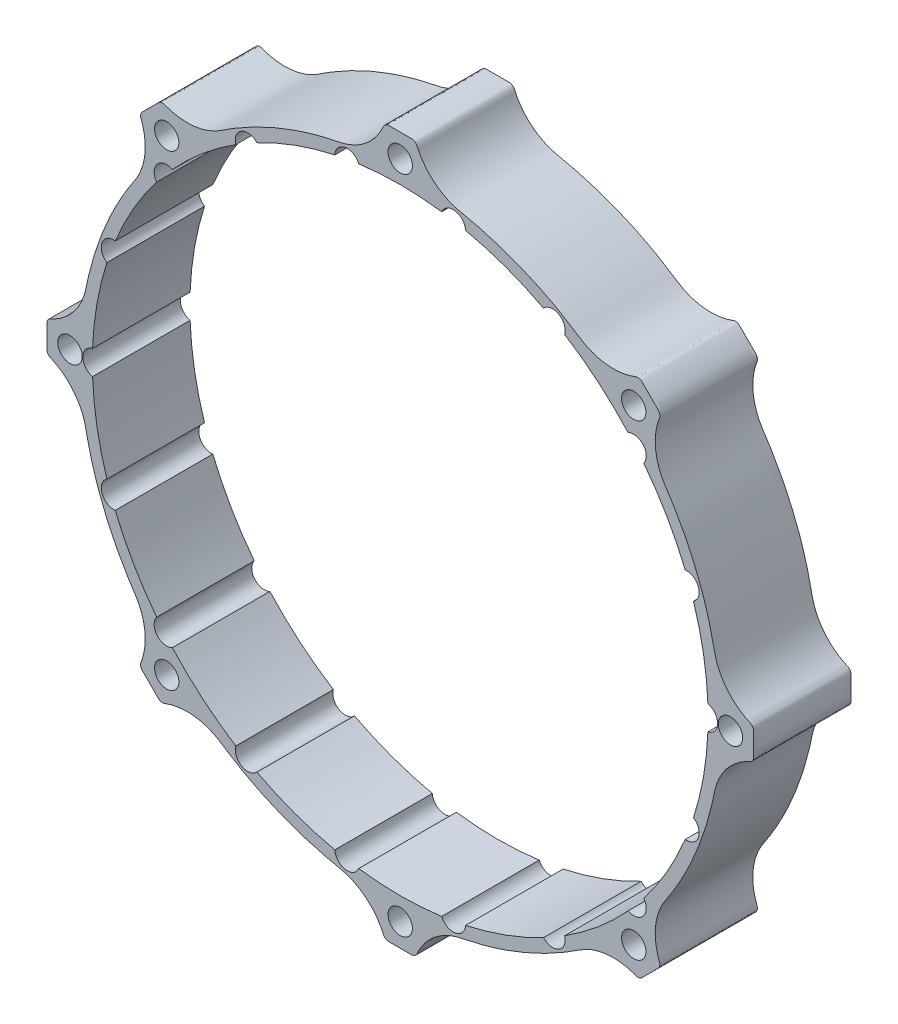
SolidWorks part; units mm, degrees
material "7075-T6, Plate (SS)"
ref_plane "Front Plane" through (0, 0, 0) normal (0, 0, 1) x (1, 0, 0)
ref_plane "Top Plane" through (0, 0, 0) normal (0, 1, 0) x (1, 0, 0)
ref_plane "Right Plane" through (0, 0, 0) normal (1, 0, 0) x (0, 0, -1)
sketch "Sketch1" plane through (0, 0, 0) normal (0, 0, 1) x (1, 0, 0)
  line L0 (0, 0) -> (0, 54.1614) construction
  line L1 (0, 0) -> (-8.6824, 49.2404) construction
  arc A0 (-6.7951, 50.0407) -> (-10.7296, 49.347) centre (-8.6824, 49.2404) ccw
  arc A36 (-10.7296, 49.347) -> (-23.5003, 44.6989) centre (0, 0) ccw
  circle A53 centre (0, 0) radius 50 construction
  arc A54 (10.7296, 49.347) -> (6.7951, 50.0407) centre (8.6824, 49.2404) ccw
  arc A55 (26.9602, 42.7012) -> (23.5003, 44.6989) centre (25, 43.3013) ccw
  arc A56 (39.939, 30.9051) -> (37.3709, 33.9656) centre (38.3022, 32.1394) ccw
  arc A57 (48.1006, 15.3814) -> (46.7341, 19.1356) centre (46.9846, 17.101) ccw
  arc A58 (50.4605, -1.9976) -> (50.4605, 1.9976) centre (50, 0) ccw
  arc A59 (46.7341, -19.1356) -> (48.1006, -15.3814) centre (46.9846, -17.101) ccw
  arc A60 (37.3709, -33.9656) -> (39.939, -30.9051) centre (38.3022, -32.1394) ccw
  arc A61 (23.5003, -44.6989) -> (26.9602, -42.7012) centre (25, -43.3013) ccw
  arc A62 (6.7951, -50.0407) -> (10.7296, -49.347) centre (8.6824, -49.2404) ccw
  arc A63 (-10.7296, -49.347) -> (-6.7951, -50.0407) centre (-8.6824, -49.2404) ccw
  arc A64 (-26.9602, -42.7012) -> (-23.5003, -44.6989) centre (-25, -43.3013) ccw
  arc A65 (-39.939, -30.9051) -> (-37.3709, -33.9656) centre (-38.3022, -32.1394) ccw
  arc A66 (-48.1006, -15.3814) -> (-46.7341, -19.1356) centre (-46.9846, -17.101) ccw
  arc A67 (-50.4605, 1.9976) -> (-50.4605, -1.9976) centre (-50, 0) ccw
  arc A68 (-46.7341, 19.1356) -> (-48.1006, 15.3814) centre (-46.9846, 17.101) ccw
  arc A69 (-37.3709, 33.9656) -> (-39.939, 30.9051) centre (-38.3022, 32.1394) ccw
  arc A70 (-23.5003, 44.6989) -> (-26.9602, 42.7012) centre (-25, 43.3013) ccw
  arc A71 (6.7951, 50.0407) -> (-6.7951, 50.0407) centre (0, 0) ccw
  arc A72 (23.5003, 44.6989) -> (10.7296, 49.347) centre (0, 0) ccw
  arc A73 (46.7341, 19.1356) -> (39.939, 30.9051) centre (0, 0) ccw
  arc A74 (37.3709, 33.9656) -> (26.9602, 42.7012) centre (0, 0) ccw
  arc A75 (50.4605, 1.9976) -> (48.1006, 15.3814) centre (0, 0) ccw
  arc A76 (48.1006, -15.3814) -> (50.4605, -1.9976) centre (0, 0) ccw
  arc A77 (39.939, -30.9051) -> (46.7341, -19.1356) centre (0, 0) ccw
  arc A78 (26.9602, -42.7012) -> (37.3709, -33.9656) centre (0, 0) ccw
  arc A79 (10.7296, -49.347) -> (23.5003, -44.6989) centre (0, 0) ccw
  arc A80 (-6.7951, -50.0407) -> (6.7951, -50.0407) centre (0, 0) ccw
  arc A81 (-23.5003, -44.6989) -> (-10.7296, -49.347) centre (0, 0) ccw
  arc A82 (-37.3709, -33.9656) -> (-26.9602, -42.7012) centre (0, 0) ccw
  arc A83 (-46.7341, -19.1356) -> (-39.939, -30.9051) centre (0, 0) ccw
  arc A84 (-50.4605, -1.9976) -> (-48.1006, -15.3814) centre (0, 0) ccw
  arc A85 (-48.1006, 15.3814) -> (-50.4605, 1.9976) centre (0, 0) ccw
  arc A86 (-39.939, 30.9051) -> (-46.7341, 19.1356) centre (0, 0) ccw
  arc A87 (-26.9602, 42.7012) -> (-37.3709, 33.9656) centre (0, 0) ccw
  spline S1 degree 3 poles (2.8952, 57.0706) (2.8663, 57.1317) (2.8097, 57.2544) (2.7303, 57.4441) (2.6534, 57.5561) (2.6097, 57.6076) (2.4833, 57.7569) (2.3195, 57.864) (2.132, 57.9198) (2.1013, 57.9289) (2.039, 57.9443) (1.9428, 57.9614) (1.8787, 57.9614) (1.8466, 57.9614) (1.8146, 57.9614) (1.7505, 57.9614) (1.6544, 57.9614) (1.5903, 57.9614) (1.5583, 57.9614) (0.5194, 57.9614) (-0.5194, 57.9614) (-1.5583, 57.9614) (-1.5903, 57.9614) (-1.6544, 57.9614) (-1.7505, 57.9614) (-1.8146, 57.9614) (-1.8466, 57.9614) (-1.8787, 57.9614) (-1.9428, 57.9614) (-2.039, 57.9443) (-2.1013, 57.9289) (-2.132, 57.9198) (-2.3195, 57.864) (-2.4833, 57.7569) (-2.6097, 57.6076) (-2.6534, 57.5561) (-2.7303, 57.4441) (-2.8097, 57.2544) (-2.8663, 57.1317) (-2.8952, 57.0706) (-3.9074, 54.9332) (-5.5869, 53.2683) (-7.7332, 52.275) (-8.2182, 52.0505) (-9.2243, 51.6793) (-10.8147, 51.3824) (-11.8574, 51.1462) (-12.3768, 51.0202) (-17.6601, 49.7386) (-22.6829, 47.6581) (-27.3251, 44.8285) (-27.7814, 44.5503) (-28.6857, 43.98) (-30.0203, 43.0653) (-30.9941, 42.6164) (-31.4958, 42.4322) (-33.8095, 41.5825) (-36.2742, 41.6063) (-38.571, 42.5005) (-38.5718, 42.5008) (-38.5735, 42.5015) (-38.576, 42.5025) (-38.5777, 42.5031) (-38.5785, 42.5034) (-38.5793, 42.5038) (-38.581, 42.5044) (-38.5835, 42.5054) (-38.5852, 42.506) (-38.586, 42.5064) (-38.591, 42.5083) (-38.596, 42.5102) (-38.601, 42.5122) (-38.6018, 42.5125) (-38.6035, 42.5132) (-38.606, 42.5141) (-38.6076, 42.5148) (-38.6085, 42.5151) (-38.6093, 42.5154) (-38.611, 42.5161) (-38.6135, 42.5171) (-38.6151, 42.5177) (-38.616, 42.518) (-38.8925, 42.6234) (-39.1877, 42.6038) (-39.4479, 42.463) (-39.4761, 42.4478) (-39.531, 42.4146) (-39.6111, 42.3586) (-39.6564, 42.3133) (-39.6791, 42.2906) (-39.7018, 42.268) (-39.7471, 42.2227) (-39.815, 42.1547) (-39.8603, 42.1094) (-39.883, 42.0867) (-40.6176, 41.3522) (-41.3522, 40.6176) (-42.0867, 39.883) (-42.1094, 39.8603) (-42.1547, 39.815) (-42.2227, 39.7471) (-42.268, 39.7018) (-42.2906, 39.6791) (-42.3133, 39.6564) (-42.3586, 39.6111) (-42.4146, 39.531) (-42.4478, 39.4761) (-42.463, 39.4479) (-42.6038, 39.1877) (-42.6234, 38.8925) (-42.518, 38.616) (-42.5177, 38.6151) (-42.5171, 38.6135) (-42.5161, 38.611) (-42.5154, 38.6093) (-42.5151, 38.6085) (-42.5148, 38.6076) (-42.5141, 38.606) (-42.5132, 38.6035) (-42.5125, 38.6018) (-42.5122, 38.601) (-42.5102, 38.596) (-42.5083, 38.591) (-42.5064, 38.586) (-42.506, 38.5852) (-42.5054, 38.5835) (-42.5044, 38.581) (-42.5038, 38.5793) (-42.5034, 38.5785) (-42.5031, 38.5777) (-42.5025, 38.576) (-42.5015, 38.5735) (-42.5008, 38.5718) (-42.5005, 38.571) (-41.6063, 36.2742) (-41.5825, 33.8095) (-42.4322, 31.4958) (-42.6164, 30.9941) (-43.0653, 30.0203) (-43.98, 28.6857) (-44.5503, 27.7814) (-44.8285, 27.3251) (-47.6581, 22.6829) (-49.7386, 17.6601) (-51.0202, 12.3768) (-51.1462, 11.8574) (-51.3824, 10.8147) (-51.6793, 9.2243) (-52.0505, 8.2182) (-52.275, 7.7332) (-53.3102, 5.4963) (-55.0698, 3.7704) (-57.3262, 2.7786) (-57.327, 2.7782) (-57.3287, 2.7775) (-57.3311, 2.7764) (-57.3328, 2.7757) (-57.3336, 2.7753) (-57.3344, 2.775) (-57.336, 2.7743) (-57.3385, 2.7732) (-57.3401, 2.7725) (-57.341, 2.7721) (-57.3459, 2.77) (-57.3508, 2.7678) (-57.3557, 2.7657) (-57.3565, 2.7653) (-57.3581, 2.7646) (-57.3606, 2.7635) (-57.3622, 2.7628) (-57.363, 2.7624) (-57.3638, 2.7621) (-57.3655, 2.7613) (-57.3679, 2.7603) (-57.3696, 2.7595) (-57.3704, 2.7592) (-57.6404, 2.6381) (-57.8354, 2.4156) (-57.9198, 2.132) (-57.9289, 2.1013) (-57.9443, 2.039) (-57.9614, 1.9428) (-57.9614, 1.8787) (-57.9614, 1.8466) (-57.9614, 1.8146) (-57.9614, 1.7505) (-57.9614, 1.6544) (-57.9614, 1.5903) (-57.9614, 1.5583) (-57.9614, 0.5194) (-57.9614, -0.5194) (-57.9614, -1.5583) (-57.9614, -1.5903) (-57.9614, -1.6544) (-57.9614, -1.7505) (-57.9614, -1.8146) (-57.9614, -1.8466) (-57.9614, -1.8787) (-57.9614, -1.9428) (-57.9443, -2.039) (-57.9289, -2.1013) (-57.9198, -2.132) (-57.8354, -2.4156) (-57.6404, -2.6381) (-57.3704, -2.7592) (-57.3696, -2.7595) (-57.3679, -2.7603) (-57.3655, -2.7613) (-57.3638, -2.7621) (-57.363, -2.7624) (-57.3622, -2.7628) (-57.3606, -2.7635) (-57.3581, -2.7646) (-57.3565, -2.7653) (-57.3557, -2.7657) (-57.3508, -2.7678) (-57.3459, -2.77) (-57.341, -2.7721) (-57.3401, -2.7725) (-57.3385, -2.7732) (-57.336, -2.7743) (-57.3344, -2.775) (-57.3336, -2.7753) (-57.3328, -2.7757) (-57.3311, -2.7764) (-57.3287, -2.7775) (-57.327, -2.7782) (-57.3262, -2.7786) (-55.0698, -3.7704) (-53.3102, -5.4963) (-52.275, -7.7332) (-52.0505, -8.2182) (-51.6793, -9.2243) (-51.3824, -10.8147) (-51.1462, -11.8574) (-51.0202, -12.3768) (-49.7386, -17.6601) (-47.6581, -22.6829) (-44.8285, -27.3251) (-44.5503, -27.7814) (-43.98, -28.6857) (-43.0653, -30.0203) (-42.6164, -30.9941) (-42.4322, -31.4958) (-41.5825, -33.8095) (-41.6063, -36.2742) (-42.5005, -38.571) (-42.5008, -38.5718) (-42.5015, -38.5735) (-42.5025, -38.576) (-42.5031, -38.5777) (-42.5034, -38.5785) (-42.5038, -38.5793) (-42.5044, -38.581) (-42.5054, -38.5835) (-42.506, -38.5852) (-42.5064, -38.586) (-42.5083, -38.591) (-42.5102, -38.596) (-42.5122, -38.601) (-42.5125, -38.6018) (-42.5132, -38.6035) (-42.5141, -38.606) (-42.5148, -38.6076) (-42.5151, -38.6085) (-42.5154, -38.6093) (-42.5161, -38.611) (-42.5171, -38.6135) (-42.5177, -38.6151) (-42.518, -38.616) (-42.6234, -38.8925) (-42.6038, -39.1877) (-42.463, -39.4479) (-42.4478, -39.4761) (-42.4146, -39.531) (-42.3586, -39.6111) (-42.3133, -39.6564) (-42.2906, -39.6791) (-42.268, -39.7018) (-42.2227, -39.7471) (-42.1547, -39.815) (-42.1094, -39.8603) (-42.0867, -39.883) (-41.3522, -40.6176) (-40.6176, -41.3522) (-39.883, -42.0867) (-39.8603, -42.1094) (-39.815, -42.1547) (-39.7471, -42.2227) (-39.7018, -42.268) (-39.6791, -42.2906) (-39.6564, -42.3133) (-39.6111, -42.3586) (-39.531, -42.4146) (-39.4761, -42.4478) (-39.4479, -42.463) (-39.1877, -42.6038) (-38.8925, -42.6234) (-38.616, -42.518) (-38.6151, -42.5177) (-38.6135, -42.5171) (-38.611, -42.5161) (-38.6093, -42.5154) (-38.6085, -42.5151) (-38.6076, -42.5148) (-38.606, -42.5141) (-38.6035, -42.5132) (-38.6018, -42.5125) (-38.601, -42.5122) (-38.596, -42.5102) (-38.591, -42.5083) (-38.586, -42.5064) (-38.5852, -42.506) (-38.5835, -42.5054) (-38.581, -42.5044) (-38.5793, -42.5038) (-38.5785, -42.5034) (-38.5777, -42.5031) (-38.576, -42.5025) (-38.5735, -42.5015) (-38.5718, -42.5008) (-38.571, -42.5005) (-36.2742, -41.6063) (-33.8095, -41.5825) (-31.4958, -42.4322) (-30.9941, -42.6164) (-30.0203, -43.0653) (-28.6857, -43.98) (-27.7814, -44.5503) (-27.3251, -44.8285) (-22.6829, -47.6581) (-17.6601, -49.7386) (-12.3768, -51.0202) (-11.8574, -51.1462) (-10.8147, -51.3824) (-9.2243, -51.6793) (-8.2182, -52.0505) (-7.7332, -52.275) (-5.4963, -53.3102) (-3.7704, -55.0698) (-2.7786, -57.3262) (-2.7782, -57.327) (-2.7775, -57.3287) (-2.7764, -57.3311) (-2.7757, -57.3328) (-2.7753, -57.3336) (-2.775, -57.3344) (-2.7743, -57.336) (-2.7732, -57.3385) (-2.7725, -57.3401) (-2.7721, -57.341) (-2.77, -57.3459) (-2.7678, -57.3508) (-2.7657, -57.3557) (-2.7653, -57.3565) (-2.7646, -57.3581) (-2.7635, -57.3606) (-2.7628, -57.3622) (-2.7624, -57.363) (-2.7621, -57.3638) (-2.7613, -57.3655) (-2.7603, -57.3679) (-2.7595, -57.3696) (-2.7592, -57.3704) (-2.6381, -57.6404) (-2.4156, -57.8354) (-2.132, -57.9198) (-2.1013, -57.9289) (-2.039, -57.9443) (-1.9428, -57.9614) (-1.8787, -57.9614) (-1.8466, -57.9614) (-1.8146, -57.9614) (-1.7505, -57.9614) (-1.6544, -57.9614) (-1.5903, -57.9614) (-1.5583, -57.9614) (-0.5194, -57.9614) (0.5194, -57.9614) (1.5583, -57.9614) (1.5903, -57.9614) (1.6544, -57.9614) (1.7505, -57.9614) (1.8146, -57.9614) (1.8466, -57.9614) (1.8787, -57.9614) (1.9428, -57.9614) (2.039, -57.9443) (2.1013, -57.9289) (2.132, -57.9198) (2.4156, -57.8354) (2.6381, -57.6404) (2.7592, -57.3704) (2.7595, -57.3696) (2.7603, -57.3679) (2.7613, -57.3655) (2.7621, -57.3638) (2.7624, -57.363) (2.7628, -57.3622) (2.7635, -57.3606) (2.7646, -57.3581) (2.7653, -57.3565) (2.7657, -57.3557) (2.7678, -57.3508) (2.77, -57.3459) (2.7721, -57.341) (2.7725, -57.3401) (2.7732, -57.3385) (2.7743, -57.336) (2.775, -57.3344) (2.7753, -57.3336) (2.7757, -57.3328) (2.7764, -57.3311) (2.7775, -57.3287) (2.7782, -57.327) (2.7786, -57.3262) (3.7704, -55.0698) (5.4963, -53.3102) (7.7332, -52.275) (8.2182, -52.0505) (9.2243, -51.6793) (10.8147, -51.3824) (11.8574, -51.1462) (12.3768, -51.0202) (17.6601, -49.7386) (22.6829, -47.6581) (27.3251, -44.8285) (27.7814, -44.5503) (28.6857, -43.98) (30.0203, -43.0653) (30.9941, -42.6164) (31.4958, -42.4322) (33.8095, -41.5825) (36.2742, -41.6063) (38.571, -42.5005) (38.5718, -42.5008) (38.5735, -42.5015) (38.576, -42.5025) (38.5777, -42.5031) (38.5785, -42.5034) (38.5793, -42.5038) (38.581, -42.5044) (38.5835, -42.5054) (38.5852, -42.506) (38.586, -42.5064) (38.591, -42.5083) (38.596, -42.5102) (38.601, -42.5122) (38.6018, -42.5125) (38.6035, -42.5132) (38.606, -42.5141) (38.6076, -42.5148) (38.6085, -42.5151) (38.6093, -42.5154) (38.611, -42.5161) (38.6135, -42.5171) (38.6151, -42.5177) (38.616, -42.518) (38.8925, -42.6234) (39.1877, -42.6038) (39.4479, -42.463) (39.4761, -42.4478) (39.531, -42.4146) (39.6111, -42.3586) (39.6564, -42.3133) (39.6791, -42.2906) (39.7018, -42.268) (39.7471, -42.2227) (39.815, -42.1547) (39.8603, -42.1094) (39.883, -42.0867) (40.6176, -41.3522) (41.3522, -40.6176) (42.0867, -39.883) (42.1094, -39.8603) (42.1547, -39.815) (42.2227, -39.7471) (42.268, -39.7018) (42.2906, -39.6791) (42.3133, -39.6564) (42.3586, -39.6111) (42.4146, -39.531) (42.4478, -39.4761) (42.463, -39.4479) (42.6038, -39.1877) (42.6234, -38.8925) (42.518, -38.616) (42.5177, -38.6151) (42.5171, -38.6135) (42.5161, -38.611) (42.5154, -38.6093) (42.5151, -38.6085) (42.5148, -38.6076) (42.5141, -38.606) (42.5132, -38.6035) (42.5125, -38.6018) (42.5122, -38.601) (42.5102, -38.596) (42.5083, -38.591) (42.5064, -38.586) (42.506, -38.5852) (42.5054, -38.5835) (42.5044, -38.581) (42.5038, -38.5793) (42.5034, -38.5785) (42.5031, -38.5777) (42.5025, -38.576) (42.5015, -38.5735) (42.5008, -38.5718) (42.5005, -38.571) (41.6063, -36.2742) (41.5825, -33.8095) (42.4322, -31.4958) (42.6164, -30.9941) (43.0653, -30.0203) (43.98, -28.6857) (44.5503, -27.7814) (44.8285, -27.3251) (47.6581, -22.6829) (49.7386, -17.6601) (51.0202, -12.3768) (51.1462, -11.8574) (51.3824, -10.8147) (51.6793, -9.2243) (52.0505, -8.2182) (52.275, -7.7332) (53.3102, -5.4963) (55.0698, -3.7704) (57.3262, -2.7786) (57.327, -2.7782) (57.3287, -2.7775) (57.3311, -2.7764) (57.3328, -2.7757) (57.3336, -2.7753) (57.3344, -2.775) (57.336, -2.7743) (57.3385, -2.7732) (57.3401, -2.7725) (57.341, -2.7721) (57.3459, -2.77) (57.3508, -2.7678) (57.3557, -2.7657) (57.3565, -2.7653) (57.3581, -2.7646) (57.3606, -2.7635) (57.3622, -2.7628) (57.363, -2.7624) (57.3638, -2.7621) (57.3655, -2.7613) (57.3679, -2.7603) (57.3696, -2.7595) (57.3704, -2.7592) (57.6404, -2.6381) (57.8354, -2.4156) (57.9198, -2.132) (57.9289, -2.1013) (57.9443, -2.039) (57.9614, -1.9428) (57.9614, -1.8787) (57.9614, -1.8466) (57.9614, -1.8146) (57.9614, -1.7505) (57.9614, -1.6544) (57.9614, -1.5903) (57.9614, -1.5583) (57.9614, -0.5194) (57.9614, 0.5194) (57.9614, 1.5583) (57.9614, 1.5903) (57.9614, 1.6544) (57.9614, 1.7505) (57.9614, 1.8146) (57.9614, 1.8466) (57.9614, 1.8787) (57.9614, 1.9428) (57.9443, 2.039) (57.9289, 2.1013) (57.9198, 2.132) (57.8354, 2.4156) (57.6404, 2.6381) (57.3704, 2.7592) (57.3696, 2.7595) (57.3679, 2.7603) (57.3655, 2.7613) (57.3638, 2.7621) (57.363, 2.7624) (57.3622, 2.7628) (57.3606, 2.7635) (57.3581, 2.7646) (57.3565, 2.7653) (57.3557, 2.7657) (57.3508, 2.7678) (57.3459, 2.77) (57.341, 2.7721) (57.3401, 2.7725) (57.3385, 2.7732) (57.336, 2.7743) (57.3344, 2.775) (57.3336, 2.7753) (57.3328, 2.7757) (57.3311, 2.7764) (57.3287, 2.7775) (57.327, 2.7782) (57.3262, 2.7786) (55.0698, 3.7704) (53.3102, 5.4963) (52.275, 7.7332) (52.0505, 8.2182) (51.6793, 9.2243) (51.3824, 10.8147) (51.1462, 11.8574) (51.0202, 12.3768) (49.7386, 17.6601) (47.6581, 22.6829) (44.8285, 27.3251) (44.5503, 27.7814) (43.98, 28.6857) (43.0653, 30.0203) (42.6164, 30.9941) (42.4322, 31.4958) (41.5825, 33.8095) (41.6063, 36.2742) (42.5005, 38.571) (42.5008, 38.5718) (42.5015, 38.5735) (42.5025, 38.576) (42.5031, 38.5777) (42.5034, 38.5785) (42.5038, 38.5793) (42.5044, 38.581) (42.5054, 38.5835) (42.506, 38.5852) (42.5064, 38.586) (42.5083, 38.591) (42.5102, 38.596) (42.5122, 38.601) (42.5125, 38.6018) (42.5132, 38.6035) (42.5141, 38.606) (42.5148, 38.6076) (42.5151, 38.6085) (42.5154, 38.6093) (42.5161, 38.611) (42.5171, 38.6135) (42.5177, 38.6151) (42.518, 38.616) (42.6234, 38.8925) (42.6038, 39.1877) (42.463, 39.4479) (42.4478, 39.4761) (42.4146, 39.531) (42.3586, 39.6111) (42.3133, 39.6564) (42.2906, 39.6791) (42.268, 39.7018) (42.2227, 39.7471) (42.1547, 39.815) (42.1094, 39.8603) (42.0867, 39.883) (41.3522, 40.6176) (40.6176, 41.3522) (39.883, 42.0867) (39.8603, 42.1094) (39.815, 42.1547) (39.7471, 42.2227) (39.7018, 42.268) (39.6791, 42.2906) (39.6564, 42.3133) (39.6111, 42.3586) (39.531, 42.4146) (39.4761, 42.4478) (39.4479, 42.463) (39.1877, 42.6038) (38.8925, 42.6234) (38.616, 42.518) (38.6151, 42.5177) (38.6135, 42.5171) (38.611, 42.5161) (38.6093, 42.5154) (38.6085, 42.5151) (38.6076, 42.5148) (38.606, 42.5141) (38.6035, 42.5132) (38.6018, 42.5125) (38.601, 42.5122) (38.596, 42.5102) (38.591, 42.5083) (38.586, 42.5064) (38.5852, 42.506) (38.5835, 42.5054) (38.581, 42.5044) (38.5793, 42.5038) (38.5785, 42.5034) (38.5777, 42.5031) (38.576, 42.5025) (38.5735, 42.5015) (38.5718, 42.5008) (38.571, 42.5005) (36.2742, 41.6063) (33.8095, 41.5825) (31.4958, 42.4322) (30.9941, 42.6164) (30.0203, 43.0653) (28.6857, 43.98) (27.7814, 44.5503) (27.3251, 44.8285) (22.6829, 47.6581) (17.6601, 49.7386) (12.3768, 51.0202) (11.8574, 51.1462) (10.8147, 51.3824) (9.2243, 51.6793) (8.2182, 52.0505) (7.7332, 52.275) (5.5869, 53.2683) (3.9074, 54.9332) (2.8952, 57.0706) (2.8663, 57.1317) (2.8097, 57.2544) knots -0.018513 0 0 0 0.000551 0.001102 0.001653 0.001653 0.001653 0.003204 0.003204 0.003204 0.003465 0.003726 0.003988 0.003988 0.003988 0.004249 0.00451 0.004771 0.004771 0.004771 0.013241 0.013241 0.013241 0.013503 0.013764 0.014025 0.014025 0.014025 0.014286 0.014548 0.014809 0.014809 0.014809 0.01636 0.01636 0.01636 0.016911 0.017462 0.018013 0.018013 0.018013 0.036526 0.036526 0.036526 0.040884 0.045242 0.049599 0.049599 0.049599 0.093572 0.093572 0.093572 0.09793 0.102288 0.106645 0.106645 0.106645 0.125875 0.125875 0.125875 0.125882 0.125889 0.125897 0.125897 0.125897 0.125904 0.125911 0.125919 0.125919 0.125919 0.125962 0.125962 0.125962 0.12597 0.125977 0.125984 0.125984 0.125984 0.125991 0.125999 0.126006 0.126006 0.126006 0.128272 0.128272 0.128272 0.128533 0.128794 0.129056 0.129056 0.129056 0.129317 0.129578 0.129839 0.129839 0.129839 0.13831 0.13831 0.13831 0.138571 0.138832 0.139093 0.139093 0.139093 0.139354 0.139616 0.139877 0.139877 0.139877 0.142143 0.142143 0.142143 0.14215 0.142157 0.142165 0.142165 0.142165 0.142172 0.142179 0.142187 0.142187 0.142187 0.14223 0.14223 0.14223 0.142238 0.142245 0.142252 0.142252 0.142252 0.142259 0.142267 0.142274 0.142274 0.142274 0.161504 0.161504 0.161504 0.165861 0.170219 0.174576 0.174576 0.174576 0.21855 0.21855 0.21855 0.222907 0.227265 0.231623 0.231623 0.231623 0.250852 0.250852 0.250852 0.25086 0.250867 0.250874 0.250874 0.250874 0.250881 0.250889 0.250896 0.250896 0.250896 0.25094 0.25094 0.25094 0.250947 0.250954 0.250961 0.250961 0.250961 0.250969 0.250976 0.250983 0.250983 0.250983 0.253249 0.253249 0.253249 0.253511 0.253772 0.254033 0.254033 0.254033 0.254294 0.254555 0.254817 0.254817 0.254817 0.263287 0.263287 0.263287 0.263548 0.263809 0.264071 0.264071 0.264071 0.264332 0.264593 0.264854 0.264854 0.264854 0.26712 0.26712 0.26712 0.267128 0.267135 0.267142 0.267142 0.267142 0.267149 0.267157 0.267164 0.267164 0.267164 0.267208 0.267208 0.267208 0.267215 0.267222 0.267229 0.267229 0.267229 0.267237 0.267244 0.267251 0.267251 0.267251 0.286481 0.286481 0.286481 0.290839 0.295196 0.299554 0.299554 0.299554 0.343527 0.343527 0.343527 0.347885 0.352242 0.3566 0.3566 0.3566 0.37583 0.37583 0.37583 0.375837 0.375844 0.375851 0.375851 0.375851 0.375859 0.375866 0.375873 0.375873 0.375873 0.375917 0.375917 0.375917 0.375924 0.375931 0.375939 0.375939 0.375939 0.375946 0.375953 0.375961 0.375961 0.375961 0.378227 0.378227 0.378227 0.378488 0.378749 0.37901 0.37901 0.37901 0.379272 0.379533 0.379794 0.379794 0.379794 0.388264 0.388264 0.388264 0.388525 0.388787 0.389048 0.389048 0.389048 0.389309 0.38957 0.389832 0.389832 0.389832 0.392098 0.392098 0.392098 0.392105 0.392112 0.392119 0.392119 0.392119 0.392127 0.392134 0.392141 0.392141 0.392141 0.392185 0.392185 0.392185 0.392192 0.3922 0.392207 0.392207 0.392207 0.392214 0.392221 0.392229 0.392229 0.392229 0.411458 0.411458 0.411458 0.415816 0.420174 0.424531 0.424531 0.424531 0.468504 0.468504 0.468504 0.472862 0.47722 0.481577 0.481577 0.481577 0.500807 0.500807 0.500807 0.500814 0.500821 0.500829 0.500829 0.500829 0.500836 0.500843 0.500851 0.500851 0.500851 0.500894 0.500894 0.500894 0.500902 0.500909 0.500916 0.500916 0.500916 0.500923 0.500931 0.500938 0.500938 0.500938 0.503204 0.503204 0.503204 0.503465 0.503726 0.503988 0.503988 0.503988 0.504249 0.50451 0.504771 0.504771 0.504771 0.513241 0.513241 0.513241 0.513503 0.513764 0.514025 0.514025 0.514025 0.514286 0.514548 0.514809 0.514809 0.514809 0.517075 0.517075 0.517075 0.517082 0.517089 0.517097 0.517097 0.517097 0.517104 0.517111 0.517119 0.517119 0.517119 0.517162 0.517162 0.517162 0.51717 0.517177 0.517184 0.517184 0.517184 0.517191 0.517199 0.517206 0.517206 0.517206 0.536436 0.536436 0.536436 0.540793 0.545151 0.549508 0.549508 0.549508 0.593482 0.593482 0.593482 0.597839 0.602197 0.606555 0.606555 0.606555 0.625784 0.625784 0.625784 0.625791 0.625799 0.625806 0.625806 0.625806 0.625813 0.625821 0.625828 0.625828 0.625828 0.625872 0.625872 0.625872 0.625879 0.625886 0.625893 0.625893 0.625893 0.625901 0.625908 0.625915 0.625915 0.625915 0.628181 0.628181 0.628181 0.628443 0.628704 0.628965 0.628965 0.628965 0.629226 0.629487 0.629749 0.629749 0.629749 0.638219 0.638219 0.638219 0.63848 0.638741 0.639003 0.639003 0.639003 0.639264 0.639525 0.639786 0.639786 0.639786 0.642052 0.642052 0.642052 0.64206 0.642067 0.642074 0.642074 0.642074 0.642081 0.642089 0.642096 0.642096 0.642096 0.64214 0.64214 0.64214 0.642147 0.642154 0.642161 0.642161 0.642161 0.642169 0.642176 0.642183 0.642183 0.642183 0.661413 0.661413 0.661413 0.665771 0.670128 0.674486 0.674486 0.674486 0.718459 0.718459 0.718459 0.722817 0.727174 0.731532 0.731532 0.731532 0.750762 0.750762 0.750762 0.750769 0.750776 0.750783 0.750783 0.750783 0.750791 0.750798 0.750805 0.750805 0.750805 0.750849 0.750849 0.750849 0.750856 0.750863 0.750871 0.750871 0.750871 0.750878 0.750885 0.750893 0.750893 0.750893 0.753159 0.753159 0.753159 0.75342 0.753681 0.753942 0.753942 0.753942 0.754204 0.754465 0.754726 0.754726 0.754726 0.763196 0.763196 0.763196 0.763457 0.763719 0.76398 0.76398 0.76398 0.764241 0.764502 0.764764 0.764764 0.764764 0.76703 0.76703 0.76703 0.767037 0.767044 0.767051 0.767051 0.767051 0.767059 0.767066 0.767073 0.767073 0.767073 0.767117 0.767117 0.767117 0.767124 0.767132 0.767139 0.767139 0.767139 0.767146 0.767153 0.767161 0.767161 0.767161 0.78639 0.78639 0.78639 0.790748 0.795106 0.799463 0.799463 0.799463 0.843436 0.843436 0.843436 0.847794 0.852152 0.856509 0.856509 0.856509 0.875739 0.875739 0.875739 0.875746 0.875753 0.875761 0.875761 0.875761 0.875768 0.875775 0.875783 0.875783 0.875783 0.875826 0.875826 0.875826 0.875834 0.875841 0.875848 0.875848 0.875848 0.875855 0.875863 0.87587 0.87587 0.87587 0.878136 0.878136 0.878136 0.878397 0.878658 0.87892 0.87892 0.87892 0.879181 0.879442 0.879703 0.879703 0.879703 0.888173 0.888173 0.888173 0.888435 0.888696 0.888957 0.888957 0.888957 0.889218 0.88948 0.889741 0.889741 0.889741 0.892007 0.892007 0.892007 0.892014 0.892021 0.892029 0.892029 0.892029 0.892036 0.892043 0.892051 0.892051 0.892051 0.892094 0.892094 0.892094 0.892102 0.892109 0.892116 0.892116 0.892116 0.892123 0.892131 0.892138 0.892138 0.892138 0.911368 0.911368 0.911368 0.915725 0.920083 0.92444 0.92444 0.92444 0.968414 0.968414 0.968414 0.972771 0.977129 0.981487 0.981487 0.981487 1 1 1 1.000551 1.001102 1.001653 weights 1 1 1 1 1 1 0.972283 0.972283 1 1 1 1 1 1 1 1 1 1 1 1 1 1 1 1 1 1 1 1 1 1 1 1 0.972283 0.972283 1 1 1 1 1 1 0.960139 0.960139 1 1 1 1 1 1 0.992037 0.992037 1 1 1 1 1 1 0.956887 0.956887 1 1 1 1 1 1 1 1 1 1 1 1 1 1 1 1 1 1 1 1 1 1 1 1 0.939305 0.939305 1 1 1 1 1 1 1 1 1 1 1 1 1 1 1 1 1 1 1 1 1 1 1 1 0.939305 0.939305 1 1 1 1 1 1 1 1 1 1 1 1 1 1 1 1 1 1 1 1 1 1 1 1 0.956887 0.956887 1 1 1 1 1 1 0.992037 0.992037 1 1 1 1 1 1 0.956887 0.956887 1 1 1 1 1 1 1 1 1 1 1 1 1 1 1 1 1 1 1 1 1 1 1 1 0.939305 0.939305 1 1 1 1 1 1 1 1 1 1 1 1 1 1 1 1 1 1 1 1 1 1 1 1 0.939305 0.939305 1 1 1 1 1 1 1 1 1 1 1 1 1 1 1 1 1 1 1 1 1 1 1 1 0.956887 0.956887 1 1 1 1 1 1 0.992037 0.992037 1 1 1 1 1 1 0.956887 0.956887 1 1 1 1 1 1 1 1 1 1 1 1 1 1 1 1 1 1 1 1 1 1 1 1 0.939305 0.939305 1 1 1 1 1 1 1 1 1 1 1 1 1 1 1 1 1 1 1 1 1 1 1 1 0.939305 0.939305 1 1 1 1 1 1 1 1 1 1 1 1 1 1 1 1 1 1 1 1 1 1 1 1 0.956887 0.956887 1 1 1 1 1 1 0.992037 0.992037 1 1 1 1 1 1 0.956887 0.956887 1 1 1 1 1 1 1 1 1 1 1 1 1 1 1 1 1 1 1 1 1 1 1 1 0.939305 0.939305 1 1 1 1 1 1 1 1 1 1 1 1 1 1 1 1 1 1 1 1 1 1 1 1 0.939305 0.939305 1 1 1 1 1 1 1 1 1 1 1 1 1 1 1 1 1 1 1 1 1 1 1 1 0.956887 0.956887 1 1 1 1 1 1 0.992037 0.992037 1 1 1 1 1 1 0.956887 0.956887 1 1 1 1 1 1 1 1 1 1 1 1 1 1 1 1 1 1 1 1 1 1 1 1 0.939305 0.939305 1 1 1 1 1 1 1 1 1 1 1 1 1 1 1 1 1 1 1 1 1 1 1 1 0.939305 0.939305 1 1 1 1 1 1 1 1 1 1 1 1 1 1 1 1 1 1 1 1 1 1 1 1 0.956887 0.956887 1 1 1 1 1 1 0.992037 0.992037 1 1 1 1 1 1 0.956887 0.956887 1 1 1 1 1 1 1 1 1 1 1 1 1 1 1 1 1 1 1 1 1 1 1 1 0.939305 0.939305 1 1 1 1 1 1 1 1 1 1 1 1 1 1 1 1 1 1 1 1 1 1 1 1 0.939305 0.939305 1 1 1 1 1 1 1 1 1 1 1 1 1 1 1 1 1 1 1 1 1 1 1 1 0.956887 0.956887 1 1 1 1 1 1 0.992037 0.992037 1 1 1 1 1 1 0.956887 0.956887 1 1 1 1 1 1 1 1 1 1 1 1 1 1 1 1 1 1 1 1 1 1 1 1 0.939305 0.939305 1 1 1 1 1 1 1 1 1 1 1 1 1 1 1 1 1 1 1 1 1 1 1 1 0.939305 0.939305 1 1 1 1 1 1 1 1 1 1 1 1 1 1 1 1 1 1 1 1 1 1 1 1 0.956887 0.956887 1 1 1 1 1 1 0.992037 0.992037 1 1 1 1 1 1 0.960139 0.960139 1 1 1 only from (2.8952, 57.0706) to (2.8952, 57.0706)
  spline S2 degree 3 poles (2.8952, 57.0706) (2.8663, 57.1317) (2.8097, 57.2544) (2.7303, 57.4441) (2.6534, 57.5561) (2.6097, 57.6076) (2.4833, 57.7569) (2.3195, 57.864) (2.132, 57.9198) (2.1013, 57.9289) (2.039, 57.9443) (1.9428, 57.9614) (1.8787, 57.9614) (1.8466, 57.9614) (1.8146, 57.9614) (1.7505, 57.9614) (1.6544, 57.9614) (1.5903, 57.9614) (1.5583, 57.9614) (0.5194, 57.9614) (-0.5194, 57.9614) (-1.5583, 57.9614) (-1.5903, 57.9614) (-1.6544, 57.9614) (-1.7505, 57.9614) (-1.8146, 57.9614) (-1.8466, 57.9614) (-1.8787, 57.9614) (-1.9428, 57.9614) (-2.039, 57.9443) (-2.1013, 57.9289) (-2.132, 57.9198) (-2.3195, 57.864) (-2.4833, 57.7569) (-2.6097, 57.6076) (-2.6534, 57.5561) (-2.7303, 57.4441) (-2.8097, 57.2544) (-2.8663, 57.1317) (-2.8952, 57.0706) (-3.9074, 54.9332) (-5.5869, 53.2683) (-7.7332, 52.275) (-8.2182, 52.0505) (-9.2243, 51.6793) (-10.8147, 51.3824) (-11.8574, 51.1462) (-12.3768, 51.0202) (-17.6601, 49.7386) (-22.6829, 47.6581) (-27.3251, 44.8285) (-27.7814, 44.5503) (-28.6857, 43.98) (-30.0203, 43.0653) (-30.9941, 42.6164) (-31.4958, 42.4322) (-33.8095, 41.5825) (-36.2742, 41.6063) (-38.571, 42.5005) (-38.5718, 42.5008) (-38.5735, 42.5015) (-38.576, 42.5025) (-38.5777, 42.5031) (-38.5785, 42.5034) (-38.5793, 42.5038) (-38.581, 42.5044) (-38.5835, 42.5054) (-38.5852, 42.506) (-38.586, 42.5064) (-38.591, 42.5083) (-38.596, 42.5102) (-38.601, 42.5122) (-38.6018, 42.5125) (-38.6035, 42.5132) (-38.606, 42.5141) (-38.6076, 42.5148) (-38.6085, 42.5151) (-38.6093, 42.5154) (-38.611, 42.5161) (-38.6135, 42.5171) (-38.6151, 42.5177) (-38.616, 42.518) (-38.8925, 42.6234) (-39.1877, 42.6038) (-39.4479, 42.463) (-39.4761, 42.4478) (-39.531, 42.4146) (-39.6111, 42.3586) (-39.6564, 42.3133) (-39.6791, 42.2906) (-39.7018, 42.268) (-39.7471, 42.2227) (-39.815, 42.1547) (-39.8603, 42.1094) (-39.883, 42.0867) (-40.6176, 41.3522) (-41.3522, 40.6176) (-42.0867, 39.883) (-42.1094, 39.8603) (-42.1547, 39.815) (-42.2227, 39.7471) (-42.268, 39.7018) (-42.2906, 39.6791) (-42.3133, 39.6564) (-42.3586, 39.6111) (-42.4146, 39.531) (-42.4478, 39.4761) (-42.463, 39.4479) (-42.6038, 39.1877) (-42.6234, 38.8925) (-42.518, 38.616) (-42.5177, 38.6151) (-42.5171, 38.6135) (-42.5161, 38.611) (-42.5154, 38.6093) (-42.5151, 38.6085) (-42.5148, 38.6076) (-42.5141, 38.606) (-42.5132, 38.6035) (-42.5125, 38.6018) (-42.5122, 38.601) (-42.5102, 38.596) (-42.5083, 38.591) (-42.5064, 38.586) (-42.506, 38.5852) (-42.5054, 38.5835) (-42.5044, 38.581) (-42.5038, 38.5793) (-42.5034, 38.5785) (-42.5031, 38.5777) (-42.5025, 38.576) (-42.5015, 38.5735) (-42.5008, 38.5718) (-42.5005, 38.571) (-41.6063, 36.2742) (-41.5825, 33.8095) (-42.4322, 31.4958) (-42.6164, 30.9941) (-43.0653, 30.0203) (-43.98, 28.6857) (-44.5503, 27.7814) (-44.8285, 27.3251) (-47.6581, 22.6829) (-49.7386, 17.6601) (-51.0202, 12.3768) (-51.1462, 11.8574) (-51.3824, 10.8147) (-51.6793, 9.2243) (-52.0505, 8.2182) (-52.275, 7.7332) (-53.3102, 5.4963) (-55.0698, 3.7704) (-57.3262, 2.7786) (-57.327, 2.7782) (-57.3287, 2.7775) (-57.3311, 2.7764) (-57.3328, 2.7757) (-57.3336, 2.7753) (-57.3344, 2.775) (-57.336, 2.7743) (-57.3385, 2.7732) (-57.3401, 2.7725) (-57.341, 2.7721) (-57.3459, 2.77) (-57.3508, 2.7678) (-57.3557, 2.7657) (-57.3565, 2.7653) (-57.3581, 2.7646) (-57.3606, 2.7635) (-57.3622, 2.7628) (-57.363, 2.7624) (-57.3638, 2.7621) (-57.3655, 2.7613) (-57.3679, 2.7603) (-57.3696, 2.7595) (-57.3704, 2.7592) (-57.6404, 2.6381) (-57.8354, 2.4156) (-57.9198, 2.132) (-57.9289, 2.1013) (-57.9443, 2.039) (-57.9614, 1.9428) (-57.9614, 1.8787) (-57.9614, 1.8466) (-57.9614, 1.8146) (-57.9614, 1.7505) (-57.9614, 1.6544) (-57.9614, 1.5903) (-57.9614, 1.5583) (-57.9614, 0.5194) (-57.9614, -0.5194) (-57.9614, -1.5583) (-57.9614, -1.5903) (-57.9614, -1.6544) (-57.9614, -1.7505) (-57.9614, -1.8146) (-57.9614, -1.8466) (-57.9614, -1.8787) (-57.9614, -1.9428) (-57.9443, -2.039) (-57.9289, -2.1013) (-57.9198, -2.132) (-57.8354, -2.4156) (-57.6404, -2.6381) (-57.3704, -2.7592) (-57.3696, -2.7595) (-57.3679, -2.7603) (-57.3655, -2.7613) (-57.3638, -2.7621) (-57.363, -2.7624) (-57.3622, -2.7628) (-57.3606, -2.7635) (-57.3581, -2.7646) (-57.3565, -2.7653) (-57.3557, -2.7657) (-57.3508, -2.7678) (-57.3459, -2.77) (-57.341, -2.7721) (-57.3401, -2.7725) (-57.3385, -2.7732) (-57.336, -2.7743) (-57.3344, -2.775) (-57.3336, -2.7753) (-57.3328, -2.7757) (-57.3311, -2.7764) (-57.3287, -2.7775) (-57.327, -2.7782) (-57.3262, -2.7786) (-55.0698, -3.7704) (-53.3102, -5.4963) (-52.275, -7.7332) (-52.0505, -8.2182) (-51.6793, -9.2243) (-51.3824, -10.8147) (-51.1462, -11.8574) (-51.0202, -12.3768) (-49.7386, -17.6601) (-47.6581, -22.6829) (-44.8285, -27.3251) (-44.5503, -27.7814) (-43.98, -28.6857) (-43.0653, -30.0203) (-42.6164, -30.9941) (-42.4322, -31.4958) (-41.5825, -33.8095) (-41.6063, -36.2742) (-42.5005, -38.571) (-42.5008, -38.5718) (-42.5015, -38.5735) (-42.5025, -38.576) (-42.5031, -38.5777) (-42.5034, -38.5785) (-42.5038, -38.5793) (-42.5044, -38.581) (-42.5054, -38.5835) (-42.506, -38.5852) (-42.5064, -38.586) (-42.5083, -38.591) (-42.5102, -38.596) (-42.5122, -38.601) (-42.5125, -38.6018) (-42.5132, -38.6035) (-42.5141, -38.606) (-42.5148, -38.6076) (-42.5151, -38.6085) (-42.5154, -38.6093) (-42.5161, -38.611) (-42.5171, -38.6135) (-42.5177, -38.6151) (-42.518, -38.616) (-42.6234, -38.8925) (-42.6038, -39.1877) (-42.463, -39.4479) (-42.4478, -39.4761) (-42.4146, -39.531) (-42.3586, -39.6111) (-42.3133, -39.6564) (-42.2906, -39.6791) (-42.268, -39.7018) (-42.2227, -39.7471) (-42.1547, -39.815) (-42.1094, -39.8603) (-42.0867, -39.883) (-41.3522, -40.6176) (-40.6176, -41.3522) (-39.883, -42.0867) (-39.8603, -42.1094) (-39.815, -42.1547) (-39.7471, -42.2227) (-39.7018, -42.268) (-39.6791, -42.2906) (-39.6564, -42.3133) (-39.6111, -42.3586) (-39.531, -42.4146) (-39.4761, -42.4478) (-39.4479, -42.463) (-39.1877, -42.6038) (-38.8925, -42.6234) (-38.616, -42.518) (-38.6151, -42.5177) (-38.6135, -42.5171) (-38.611, -42.5161) (-38.6093, -42.5154) (-38.6085, -42.5151) (-38.6076, -42.5148) (-38.606, -42.5141) (-38.6035, -42.5132) (-38.6018, -42.5125) (-38.601, -42.5122) (-38.596, -42.5102) (-38.591, -42.5083) (-38.586, -42.5064) (-38.5852, -42.506) (-38.5835, -42.5054) (-38.581, -42.5044) (-38.5793, -42.5038) (-38.5785, -42.5034) (-38.5777, -42.5031) (-38.576, -42.5025) (-38.5735, -42.5015) (-38.5718, -42.5008) (-38.571, -42.5005) (-36.2742, -41.6063) (-33.8095, -41.5825) (-31.4958, -42.4322) (-30.9941, -42.6164) (-30.0203, -43.0653) (-28.6857, -43.98) (-27.7814, -44.5503) (-27.3251, -44.8285) (-22.6829, -47.6581) (-17.6601, -49.7386) (-12.3768, -51.0202) (-11.8574, -51.1462) (-10.8147, -51.3824) (-9.2243, -51.6793) (-8.2182, -52.0505) (-7.7332, -52.275) (-5.4963, -53.3102) (-3.7704, -55.0698) (-2.7786, -57.3262) (-2.7782, -57.327) (-2.7775, -57.3287) (-2.7764, -57.3311) (-2.7757, -57.3328) (-2.7753, -57.3336) (-2.775, -57.3344) (-2.7743, -57.336) (-2.7732, -57.3385) (-2.7725, -57.3401) (-2.7721, -57.341) (-2.77, -57.3459) (-2.7678, -57.3508) (-2.7657, -57.3557) (-2.7653, -57.3565) (-2.7646, -57.3581) (-2.7635, -57.3606) (-2.7628, -57.3622) (-2.7624, -57.363) (-2.7621, -57.3638) (-2.7613, -57.3655) (-2.7603, -57.3679) (-2.7595, -57.3696) (-2.7592, -57.3704) (-2.6381, -57.6404) (-2.4156, -57.8354) (-2.132, -57.9198) (-2.1013, -57.9289) (-2.039, -57.9443) (-1.9428, -57.9614) (-1.8787, -57.9614) (-1.8466, -57.9614) (-1.8146, -57.9614) (-1.7505, -57.9614) (-1.6544, -57.9614) (-1.5903, -57.9614) (-1.5583, -57.9614) (-0.5194, -57.9614) (0.5194, -57.9614) (1.5583, -57.9614) (1.5903, -57.9614) (1.6544, -57.9614) (1.7505, -57.9614) (1.8146, -57.9614) (1.8466, -57.9614) (1.8787, -57.9614) (1.9428, -57.9614) (2.039, -57.9443) (2.1013, -57.9289) (2.132, -57.9198) (2.4156, -57.8354) (2.6381, -57.6404) (2.7592, -57.3704) (2.7595, -57.3696) (2.7603, -57.3679) (2.7613, -57.3655) (2.7621, -57.3638) (2.7624, -57.363) (2.7628, -57.3622) (2.7635, -57.3606) (2.7646, -57.3581) (2.7653, -57.3565) (2.7657, -57.3557) (2.7678, -57.3508) (2.77, -57.3459) (2.7721, -57.341) (2.7725, -57.3401) (2.7732, -57.3385) (2.7743, -57.336) (2.775, -57.3344) (2.7753, -57.3336) (2.7757, -57.3328) (2.7764, -57.3311) (2.7775, -57.3287) (2.7782, -57.327) (2.7786, -57.3262) (3.7704, -55.0698) (5.4963, -53.3102) (7.7332, -52.275) (8.2182, -52.0505) (9.2243, -51.6793) (10.8147, -51.3824) (11.8574, -51.1462) (12.3768, -51.0202) (17.6601, -49.7386) (22.6829, -47.6581) (27.3251, -44.8285) (27.7814, -44.5503) (28.6857, -43.98) (30.0203, -43.0653) (30.9941, -42.6164) (31.4958, -42.4322) (33.8095, -41.5825) (36.2742, -41.6063) (38.571, -42.5005) (38.5718, -42.5008) (38.5735, -42.5015) (38.576, -42.5025) (38.5777, -42.5031) (38.5785, -42.5034) (38.5793, -42.5038) (38.581, -42.5044) (38.5835, -42.5054) (38.5852, -42.506) (38.586, -42.5064) (38.591, -42.5083) (38.596, -42.5102) (38.601, -42.5122) (38.6018, -42.5125) (38.6035, -42.5132) (38.606, -42.5141) (38.6076, -42.5148) (38.6085, -42.5151) (38.6093, -42.5154) (38.611, -42.5161) (38.6135, -42.5171) (38.6151, -42.5177) (38.616, -42.518) (38.8925, -42.6234) (39.1877, -42.6038) (39.4479, -42.463) (39.4761, -42.4478) (39.531, -42.4146) (39.6111, -42.3586) (39.6564, -42.3133) (39.6791, -42.2906) (39.7018, -42.268) (39.7471, -42.2227) (39.815, -42.1547) (39.8603, -42.1094) (39.883, -42.0867) (40.6176, -41.3522) (41.3522, -40.6176) (42.0867, -39.883) (42.1094, -39.8603) (42.1547, -39.815) (42.2227, -39.7471) (42.268, -39.7018) (42.2906, -39.6791) (42.3133, -39.6564) (42.3586, -39.6111) (42.4146, -39.531) (42.4478, -39.4761) (42.463, -39.4479) (42.6038, -39.1877) (42.6234, -38.8925) (42.518, -38.616) (42.5177, -38.6151) (42.5171, -38.6135) (42.5161, -38.611) (42.5154, -38.6093) (42.5151, -38.6085) (42.5148, -38.6076) (42.5141, -38.606) (42.5132, -38.6035) (42.5125, -38.6018) (42.5122, -38.601) (42.5102, -38.596) (42.5083, -38.591) (42.5064, -38.586) (42.506, -38.5852) (42.5054, -38.5835) (42.5044, -38.581) (42.5038, -38.5793) (42.5034, -38.5785) (42.5031, -38.5777) (42.5025, -38.576) (42.5015, -38.5735) (42.5008, -38.5718) (42.5005, -38.571) (41.6063, -36.2742) (41.5825, -33.8095) (42.4322, -31.4958) (42.6164, -30.9941) (43.0653, -30.0203) (43.98, -28.6857) (44.5503, -27.7814) (44.8285, -27.3251) (47.6581, -22.6829) (49.7386, -17.6601) (51.0202, -12.3768) (51.1462, -11.8574) (51.3824, -10.8147) (51.6793, -9.2243) (52.0505, -8.2182) (52.275, -7.7332) (53.3102, -5.4963) (55.0698, -3.7704) (57.3262, -2.7786) (57.327, -2.7782) (57.3287, -2.7775) (57.3311, -2.7764) (57.3328, -2.7757) (57.3336, -2.7753) (57.3344, -2.775) (57.336, -2.7743) (57.3385, -2.7732) (57.3401, -2.7725) (57.341, -2.7721) (57.3459, -2.77) (57.3508, -2.7678) (57.3557, -2.7657) (57.3565, -2.7653) (57.3581, -2.7646) (57.3606, -2.7635) (57.3622, -2.7628) (57.363, -2.7624) (57.3638, -2.7621) (57.3655, -2.7613) (57.3679, -2.7603) (57.3696, -2.7595) (57.3704, -2.7592) (57.6404, -2.6381) (57.8354, -2.4156) (57.9198, -2.132) (57.9289, -2.1013) (57.9443, -2.039) (57.9614, -1.9428) (57.9614, -1.8787) (57.9614, -1.8466) (57.9614, -1.8146) (57.9614, -1.7505) (57.9614, -1.6544) (57.9614, -1.5903) (57.9614, -1.5583) (57.9614, -0.5194) (57.9614, 0.5194) (57.9614, 1.5583) (57.9614, 1.5903) (57.9614, 1.6544) (57.9614, 1.7505) (57.9614, 1.8146) (57.9614, 1.8466) (57.9614, 1.8787) (57.9614, 1.9428) (57.9443, 2.039) (57.9289, 2.1013) (57.9198, 2.132) (57.8354, 2.4156) (57.6404, 2.6381) (57.3704, 2.7592) (57.3696, 2.7595) (57.3679, 2.7603) (57.3655, 2.7613) (57.3638, 2.7621) (57.363, 2.7624) (57.3622, 2.7628) (57.3606, 2.7635) (57.3581, 2.7646) (57.3565, 2.7653) (57.3557, 2.7657) (57.3508, 2.7678) (57.3459, 2.77) (57.341, 2.7721) (57.3401, 2.7725) (57.3385, 2.7732) (57.336, 2.7743) (57.3344, 2.775) (57.3336, 2.7753) (57.3328, 2.7757) (57.3311, 2.7764) (57.3287, 2.7775) (57.327, 2.7782) (57.3262, 2.7786) (55.0698, 3.7704) (53.3102, 5.4963) (52.275, 7.7332) (52.0505, 8.2182) (51.6793, 9.2243) (51.3824, 10.8147) (51.1462, 11.8574) (51.0202, 12.3768) (49.7386, 17.6601) (47.6581, 22.6829) (44.8285, 27.3251) (44.5503, 27.7814) (43.98, 28.6857) (43.0653, 30.0203) (42.6164, 30.9941) (42.4322, 31.4958) (41.5825, 33.8095) (41.6063, 36.2742) (42.5005, 38.571) (42.5008, 38.5718) (42.5015, 38.5735) (42.5025, 38.576) (42.5031, 38.5777) (42.5034, 38.5785) (42.5038, 38.5793) (42.5044, 38.581) (42.5054, 38.5835) (42.506, 38.5852) (42.5064, 38.586) (42.5083, 38.591) (42.5102, 38.596) (42.5122, 38.601) (42.5125, 38.6018) (42.5132, 38.6035) (42.5141, 38.606) (42.5148, 38.6076) (42.5151, 38.6085) (42.5154, 38.6093) (42.5161, 38.611) (42.5171, 38.6135) (42.5177, 38.6151) (42.518, 38.616) (42.6234, 38.8925) (42.6038, 39.1877) (42.463, 39.4479) (42.4478, 39.4761) (42.4146, 39.531) (42.3586, 39.6111) (42.3133, 39.6564) (42.2906, 39.6791) (42.268, 39.7018) (42.2227, 39.7471) (42.1547, 39.815) (42.1094, 39.8603) (42.0867, 39.883) (41.3522, 40.6176) (40.6176, 41.3522) (39.883, 42.0867) (39.8603, 42.1094) (39.815, 42.1547) (39.7471, 42.2227) (39.7018, 42.268) (39.6791, 42.2906) (39.6564, 42.3133) (39.6111, 42.3586) (39.531, 42.4146) (39.4761, 42.4478) (39.4479, 42.463) (39.1877, 42.6038) (38.8925, 42.6234) (38.616, 42.518) (38.6151, 42.5177) (38.6135, 42.5171) (38.611, 42.5161) (38.6093, 42.5154) (38.6085, 42.5151) (38.6076, 42.5148) (38.606, 42.5141) (38.6035, 42.5132) (38.6018, 42.5125) (38.601, 42.5122) (38.596, 42.5102) (38.591, 42.5083) (38.586, 42.5064) (38.5852, 42.506) (38.5835, 42.5054) (38.581, 42.5044) (38.5793, 42.5038) (38.5785, 42.5034) (38.5777, 42.5031) (38.576, 42.5025) (38.5735, 42.5015) (38.5718, 42.5008) (38.571, 42.5005) (36.2742, 41.6063) (33.8095, 41.5825) (31.4958, 42.4322) (30.9941, 42.6164) (30.0203, 43.0653) (28.6857, 43.98) (27.7814, 44.5503) (27.3251, 44.8285) (22.6829, 47.6581) (17.6601, 49.7386) (12.3768, 51.0202) (11.8574, 51.1462) (10.8147, 51.3824) (9.2243, 51.6793) (8.2182, 52.0505) (7.7332, 52.275) (5.5869, 53.2683) (3.9074, 54.9332) (2.8952, 57.0706) (2.8663, 57.1317) (2.8097, 57.2544) knots -0.018513 0 0 0 0.000551 0.001102 0.001653 0.001653 0.001653 0.003204 0.003204 0.003204 0.003465 0.003726 0.003988 0.003988 0.003988 0.004249 0.00451 0.004771 0.004771 0.004771 0.013241 0.013241 0.013241 0.013503 0.013764 0.014025 0.014025 0.014025 0.014286 0.014548 0.014809 0.014809 0.014809 0.01636 0.01636 0.01636 0.016911 0.017462 0.018013 0.018013 0.018013 0.036526 0.036526 0.036526 0.040884 0.045242 0.049599 0.049599 0.049599 0.093572 0.093572 0.093572 0.09793 0.102288 0.106645 0.106645 0.106645 0.125875 0.125875 0.125875 0.125882 0.125889 0.125897 0.125897 0.125897 0.125904 0.125911 0.125919 0.125919 0.125919 0.125962 0.125962 0.125962 0.12597 0.125977 0.125984 0.125984 0.125984 0.125991 0.125999 0.126006 0.126006 0.126006 0.128272 0.128272 0.128272 0.128533 0.128794 0.129056 0.129056 0.129056 0.129317 0.129578 0.129839 0.129839 0.129839 0.13831 0.13831 0.13831 0.138571 0.138832 0.139093 0.139093 0.139093 0.139354 0.139616 0.139877 0.139877 0.139877 0.142143 0.142143 0.142143 0.14215 0.142157 0.142165 0.142165 0.142165 0.142172 0.142179 0.142187 0.142187 0.142187 0.14223 0.14223 0.14223 0.142238 0.142245 0.142252 0.142252 0.142252 0.142259 0.142267 0.142274 0.142274 0.142274 0.161504 0.161504 0.161504 0.165861 0.170219 0.174576 0.174576 0.174576 0.21855 0.21855 0.21855 0.222907 0.227265 0.231623 0.231623 0.231623 0.250852 0.250852 0.250852 0.25086 0.250867 0.250874 0.250874 0.250874 0.250881 0.250889 0.250896 0.250896 0.250896 0.25094 0.25094 0.25094 0.250947 0.250954 0.250961 0.250961 0.250961 0.250969 0.250976 0.250983 0.250983 0.250983 0.253249 0.253249 0.253249 0.253511 0.253772 0.254033 0.254033 0.254033 0.254294 0.254555 0.254817 0.254817 0.254817 0.263287 0.263287 0.263287 0.263548 0.263809 0.264071 0.264071 0.264071 0.264332 0.264593 0.264854 0.264854 0.264854 0.26712 0.26712 0.26712 0.267128 0.267135 0.267142 0.267142 0.267142 0.267149 0.267157 0.267164 0.267164 0.267164 0.267208 0.267208 0.267208 0.267215 0.267222 0.267229 0.267229 0.267229 0.267237 0.267244 0.267251 0.267251 0.267251 0.286481 0.286481 0.286481 0.290839 0.295196 0.299554 0.299554 0.299554 0.343527 0.343527 0.343527 0.347885 0.352242 0.3566 0.3566 0.3566 0.37583 0.37583 0.37583 0.375837 0.375844 0.375851 0.375851 0.375851 0.375859 0.375866 0.375873 0.375873 0.375873 0.375917 0.375917 0.375917 0.375924 0.375931 0.375939 0.375939 0.375939 0.375946 0.375953 0.375961 0.375961 0.375961 0.378227 0.378227 0.378227 0.378488 0.378749 0.37901 0.37901 0.37901 0.379272 0.379533 0.379794 0.379794 0.379794 0.388264 0.388264 0.388264 0.388525 0.388787 0.389048 0.389048 0.389048 0.389309 0.38957 0.389832 0.389832 0.389832 0.392098 0.392098 0.392098 0.392105 0.392112 0.392119 0.392119 0.392119 0.392127 0.392134 0.392141 0.392141 0.392141 0.392185 0.392185 0.392185 0.392192 0.3922 0.392207 0.392207 0.392207 0.392214 0.392221 0.392229 0.392229 0.392229 0.411458 0.411458 0.411458 0.415816 0.420174 0.424531 0.424531 0.424531 0.468504 0.468504 0.468504 0.472862 0.47722 0.481577 0.481577 0.481577 0.500807 0.500807 0.500807 0.500814 0.500821 0.500829 0.500829 0.500829 0.500836 0.500843 0.500851 0.500851 0.500851 0.500894 0.500894 0.500894 0.500902 0.500909 0.500916 0.500916 0.500916 0.500923 0.500931 0.500938 0.500938 0.500938 0.503204 0.503204 0.503204 0.503465 0.503726 0.503988 0.503988 0.503988 0.504249 0.50451 0.504771 0.504771 0.504771 0.513241 0.513241 0.513241 0.513503 0.513764 0.514025 0.514025 0.514025 0.514286 0.514548 0.514809 0.514809 0.514809 0.517075 0.517075 0.517075 0.517082 0.517089 0.517097 0.517097 0.517097 0.517104 0.517111 0.517119 0.517119 0.517119 0.517162 0.517162 0.517162 0.51717 0.517177 0.517184 0.517184 0.517184 0.517191 0.517199 0.517206 0.517206 0.517206 0.536436 0.536436 0.536436 0.540793 0.545151 0.549508 0.549508 0.549508 0.593482 0.593482 0.593482 0.597839 0.602197 0.606555 0.606555 0.606555 0.625784 0.625784 0.625784 0.625791 0.625799 0.625806 0.625806 0.625806 0.625813 0.625821 0.625828 0.625828 0.625828 0.625872 0.625872 0.625872 0.625879 0.625886 0.625893 0.625893 0.625893 0.625901 0.625908 0.625915 0.625915 0.625915 0.628181 0.628181 0.628181 0.628443 0.628704 0.628965 0.628965 0.628965 0.629226 0.629487 0.629749 0.629749 0.629749 0.638219 0.638219 0.638219 0.63848 0.638741 0.639003 0.639003 0.639003 0.639264 0.639525 0.639786 0.639786 0.639786 0.642052 0.642052 0.642052 0.64206 0.642067 0.642074 0.642074 0.642074 0.642081 0.642089 0.642096 0.642096 0.642096 0.64214 0.64214 0.64214 0.642147 0.642154 0.642161 0.642161 0.642161 0.642169 0.642176 0.642183 0.642183 0.642183 0.661413 0.661413 0.661413 0.665771 0.670128 0.674486 0.674486 0.674486 0.718459 0.718459 0.718459 0.722817 0.727174 0.731532 0.731532 0.731532 0.750762 0.750762 0.750762 0.750769 0.750776 0.750783 0.750783 0.750783 0.750791 0.750798 0.750805 0.750805 0.750805 0.750849 0.750849 0.750849 0.750856 0.750863 0.750871 0.750871 0.750871 0.750878 0.750885 0.750893 0.750893 0.750893 0.753159 0.753159 0.753159 0.75342 0.753681 0.753942 0.753942 0.753942 0.754204 0.754465 0.754726 0.754726 0.754726 0.763196 0.763196 0.763196 0.763457 0.763719 0.76398 0.76398 0.76398 0.764241 0.764502 0.764764 0.764764 0.764764 0.76703 0.76703 0.76703 0.767037 0.767044 0.767051 0.767051 0.767051 0.767059 0.767066 0.767073 0.767073 0.767073 0.767117 0.767117 0.767117 0.767124 0.767132 0.767139 0.767139 0.767139 0.767146 0.767153 0.767161 0.767161 0.767161 0.78639 0.78639 0.78639 0.790748 0.795106 0.799463 0.799463 0.799463 0.843436 0.843436 0.843436 0.847794 0.852152 0.856509 0.856509 0.856509 0.875739 0.875739 0.875739 0.875746 0.875753 0.875761 0.875761 0.875761 0.875768 0.875775 0.875783 0.875783 0.875783 0.875826 0.875826 0.875826 0.875834 0.875841 0.875848 0.875848 0.875848 0.875855 0.875863 0.87587 0.87587 0.87587 0.878136 0.878136 0.878136 0.878397 0.878658 0.87892 0.87892 0.87892 0.879181 0.879442 0.879703 0.879703 0.879703 0.888173 0.888173 0.888173 0.888435 0.888696 0.888957 0.888957 0.888957 0.889218 0.88948 0.889741 0.889741 0.889741 0.892007 0.892007 0.892007 0.892014 0.892021 0.892029 0.892029 0.892029 0.892036 0.892043 0.892051 0.892051 0.892051 0.892094 0.892094 0.892094 0.892102 0.892109 0.892116 0.892116 0.892116 0.892123 0.892131 0.892138 0.892138 0.892138 0.911368 0.911368 0.911368 0.915725 0.920083 0.92444 0.92444 0.92444 0.968414 0.968414 0.968414 0.972771 0.977129 0.981487 0.981487 0.981487 1 1 1 1.000551 1.001102 1.001653 weights 1 1 1 1 1 1 0.972283 0.972283 1 1 1 1 1 1 1 1 1 1 1 1 1 1 1 1 1 1 1 1 1 1 1 1 0.972283 0.972283 1 1 1 1 1 1 0.960139 0.960139 1 1 1 1 1 1 0.992037 0.992037 1 1 1 1 1 1 0.956887 0.956887 1 1 1 1 1 1 1 1 1 1 1 1 1 1 1 1 1 1 1 1 1 1 1 1 0.939305 0.939305 1 1 1 1 1 1 1 1 1 1 1 1 1 1 1 1 1 1 1 1 1 1 1 1 0.939305 0.939305 1 1 1 1 1 1 1 1 1 1 1 1 1 1 1 1 1 1 1 1 1 1 1 1 0.956887 0.956887 1 1 1 1 1 1 0.992037 0.992037 1 1 1 1 1 1 0.956887 0.956887 1 1 1 1 1 1 1 1 1 1 1 1 1 1 1 1 1 1 1 1 1 1 1 1 0.939305 0.939305 1 1 1 1 1 1 1 1 1 1 1 1 1 1 1 1 1 1 1 1 1 1 1 1 0.939305 0.939305 1 1 1 1 1 1 1 1 1 1 1 1 1 1 1 1 1 1 1 1 1 1 1 1 0.956887 0.956887 1 1 1 1 1 1 0.992037 0.992037 1 1 1 1 1 1 0.956887 0.956887 1 1 1 1 1 1 1 1 1 1 1 1 1 1 1 1 1 1 1 1 1 1 1 1 0.939305 0.939305 1 1 1 1 1 1 1 1 1 1 1 1 1 1 1 1 1 1 1 1 1 1 1 1 0.939305 0.939305 1 1 1 1 1 1 1 1 1 1 1 1 1 1 1 1 1 1 1 1 1 1 1 1 0.956887 0.956887 1 1 1 1 1 1 0.992037 0.992037 1 1 1 1 1 1 0.956887 0.956887 1 1 1 1 1 1 1 1 1 1 1 1 1 1 1 1 1 1 1 1 1 1 1 1 0.939305 0.939305 1 1 1 1 1 1 1 1 1 1 1 1 1 1 1 1 1 1 1 1 1 1 1 1 0.939305 0.939305 1 1 1 1 1 1 1 1 1 1 1 1 1 1 1 1 1 1 1 1 1 1 1 1 0.956887 0.956887 1 1 1 1 1 1 0.992037 0.992037 1 1 1 1 1 1 0.956887 0.956887 1 1 1 1 1 1 1 1 1 1 1 1 1 1 1 1 1 1 1 1 1 1 1 1 0.939305 0.939305 1 1 1 1 1 1 1 1 1 1 1 1 1 1 1 1 1 1 1 1 1 1 1 1 0.939305 0.939305 1 1 1 1 1 1 1 1 1 1 1 1 1 1 1 1 1 1 1 1 1 1 1 1 0.956887 0.956887 1 1 1 1 1 1 0.992037 0.992037 1 1 1 1 1 1 0.956887 0.956887 1 1 1 1 1 1 1 1 1 1 1 1 1 1 1 1 1 1 1 1 1 1 1 1 0.939305 0.939305 1 1 1 1 1 1 1 1 1 1 1 1 1 1 1 1 1 1 1 1 1 1 1 1 0.939305 0.939305 1 1 1 1 1 1 1 1 1 1 1 1 1 1 1 1 1 1 1 1 1 1 1 1 0.956887 0.956887 1 1 1 1 1 1 0.992037 0.992037 1 1 1 1 1 1 0.956887 0.956887 1 1 1 1 1 1 1 1 1 1 1 1 1 1 1 1 1 1 1 1 1 1 1 1 0.939305 0.939305 1 1 1 1 1 1 1 1 1 1 1 1 1 1 1 1 1 1 1 1 1 1 1 1 0.939305 0.939305 1 1 1 1 1 1 1 1 1 1 1 1 1 1 1 1 1 1 1 1 1 1 1 1 0.956887 0.956887 1 1 1 1 1 1 0.992037 0.992037 1 1 1 1 1 1 0.960139 0.960139 1 1 1 only from (2.8952, 57.0706) to (2.8952, 57.0706)
  point P1 (0, 0)
  point P2 (0, 54.1614)
  point P30 (-8.6824, 49.2404)
  point P86 (0, 0)
  dimension "D2" = 100
  dimension "D3" = 2.05
  dimension "D5" = 50.5
  dimension "D4" = 10
  dimension "D7" = 54.1614
  dimension "D1" = 0
  dimension "D6" = 18
extrude "Boss-Extrude1" add sketch "Sketch1" along normal blind 16
hole_wizard "Ø4.0mm Dowel Hole1" positions "Sketch4" profile "Sketch5" hole size "Ø4.0" standard "ISO" end condition through all
sketch "Sketch4" plane through (0, 0, 0) normal (0, 0, -1) x (-1, 0, 0)
  point P0 (0, 54.1614)
sketch "Sketch5" plane through (0, 54.1614, 0) normal (1, 0, 0) x (0, 1, 0)
  line L0 (0, 0) -> (0, 16)
  line L1 (0, 16) -> (2, 16)
  line L2 (2, 16) -> (2, 0.025)
  line L3 (2, 0.025) -> (2.025, 0)
  line L5 (2.025, 0) -> (0, 0)
  line L6 (-2, 0.025) -> (-2.025, 0) construction
  line L11 (0, -6.35) -> (0, 107.95) construction
  dimension "Thru Hole Dia." = 4
  dimension "Thru Hole Depth" = 16
  dimension "Near C'Sink Dia." = 4.05
  dimension "Near C'Sink Angle" = 90
pattern_circular "CirPattern1" count 8 over 360 about axis through (0, 0, 16) along (0, 0, -1) of "Ø4.0mm Dowel Hole1"
